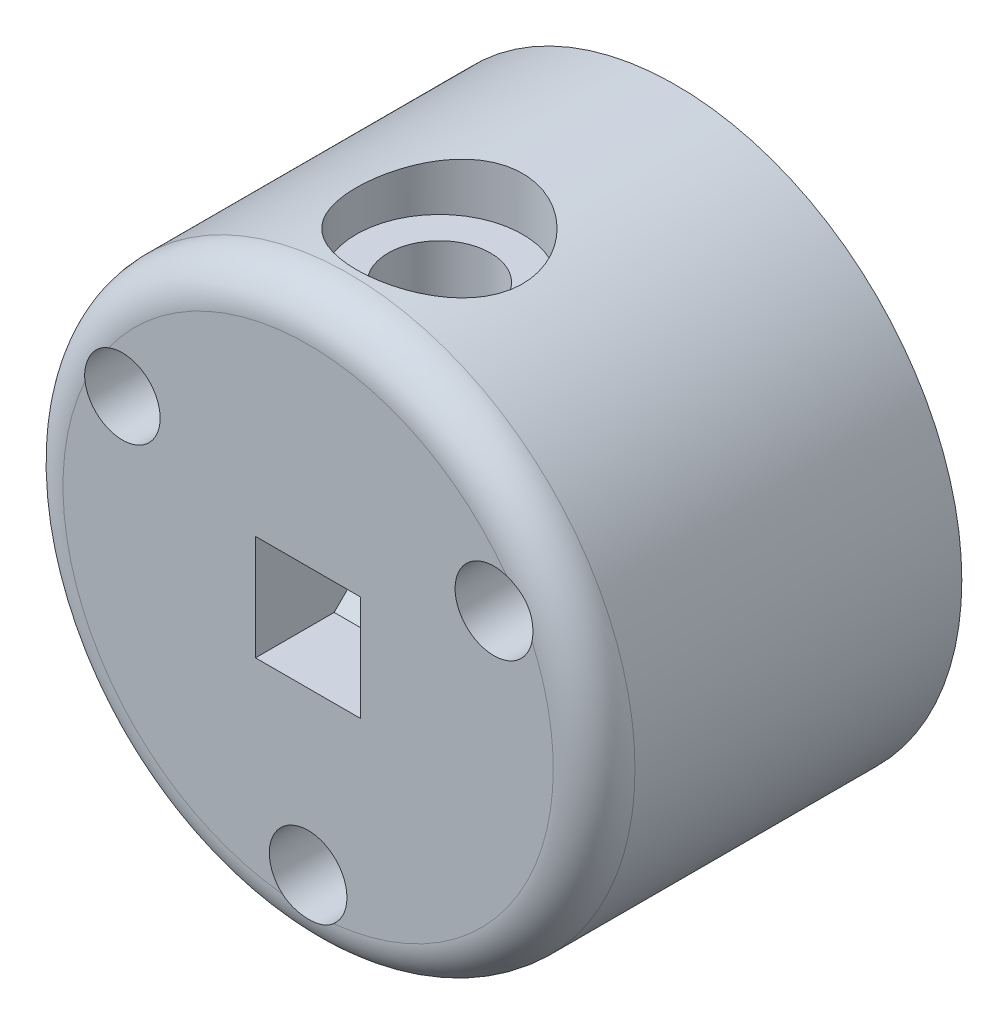
SolidWorks part; units mm, degrees
material "ABS"
ref_plane "前视基准面" through (0, 0, 0) normal (0, 0, 1) x (1, 0, 0)
ref_plane "上视基准面" through (0, 0, 0) normal (0, 1, 0) x (1, 0, 0)
ref_plane "右视基准面" through (0, 0, 0) normal (1, 0, 0) x (0, 0, -1)
sketch "草图1" plane through (0, 0, 0) normal (0, 0, 1) x (1, 0, 0)
  circle A0 centre (0, 0) radius 14
  dimension "D1" = 28
extrude "凸台-拉伸1" add sketch "草图1" along normal blind 22
sketch "草图2" plane through (0, 0, 22) normal (0, 0, 1) x (1, 0, 0)
  line L1 (0, 10.5) -> (-9.0933, 5.25) construction
  line L2 (-9.0933, 5.25) -> (-9.0933, -5.25) construction
  line L3 (-9.0933, -5.25) -> (0, -10.5) construction
  line L4 (0, -10.5) -> (9.0933, -5.25) construction
  line L5 (9.0933, -5.25) -> (9.0933, 5.25) construction
  line L6 (9.0933, 5.25) -> (0, 10.5) construction
  circle A0 centre (0, 0) radius 10.5 construction
  circle A2 centre (-9.0933, 5.25) radius 1.1
  circle A4 centre (9.0933, 5.25) radius 1.1
  circle A6 centre (0, -10.5) radius 1.1
  dimension "D1" = 21
sketch "草图3" plane through (0, 0, 0) normal (0, 0, -1) x (-1, 0, 0)
  circle A0 centre (0, 0) radius 7.35
  dimension "D1" = 14.7
extrude "切除-拉伸1" cut sketch "草图3" against normal blind 6
extrude "切除-拉伸2" cut sketch "草图2" against normal blind 32
sketch "草图4" plane through (0, 0, 22) normal (0, 0, 1) x (1, 0, 0)
  circle A7 centre (9.0933, 5.25) radius 1.9
  circle A9 centre (0, -10.5) radius 1.9
  circle A11 centre (-9.0933, 5.25) radius 1.85
  dimension "D1" = 3.8
extrude "切除-拉伸3" cut sketch "草图4" against normal blind 19
sketch "草图5" plane through (0, 0, 22) normal (0, 0, 1) x (1, 0, 0)
  line L1 (-2.575, -2.575) -> (2.575, -2.575)
  line L2 (-2.575, -2.575) -> (-2.575, 2.575)
  line L3 (-2.575, 2.575) -> (2.575, 2.575)
  line L4 (2.575, -2.575) -> (2.575, 2.575)
  line L5 (-2.575, -2.575) -> (2.575, 2.575) construction
  line L6 (-2.575, 2.575) -> (2.575, -2.575) construction
  point P0 (0, 0)
  dimension "D1" = 5.15
  dimension "D2" = 5.15
extrude "切除-拉伸4" cut sketch "草图5" against normal blind 13
sketch "草图6" plane through (-2.575, 0, 0) normal (1, 0, 0) x (0, 0, -1)
  line L0 (-9, -2.575) -> (-14.15, -2.575)
  line L1 (-9, -2.575) -> (-22, -2.575) construction
  line L2 (-14.15, -2.575) -> (-9, 2.575)
  line L3 (-9, 2.575) -> (-9, -2.575)
  dimension "D1" = 45
extrude "凸台-拉伸2" add sketch "草图6" along normal up to next
sketch "草图10" plane through (0, 0, 22) normal (0, 0, 1) x (1, 0, 0)
  line L0 (4, 13.4164) -> (-4, 13.4164) construction
  line L1 (2.575, 2.575) -> (-2.575, 2.575) construction
  circle A0 centre (0, 0) radius 14 construction
  dimension "D1" = 0
  dimension "D2" = 8
ref_plane "基准面1" through (0, 13.4164, 0) normal (0, 1, 0) x (1, 0, 0)
sketch "草图12" plane through (0, 0, 22) normal (0, 0, 1) x (1, 0, 0)
  circle A0 centre (0, 0) radius 19.2084
extrude "切除-拉伸9" cut sketch "草图12" against normal blind 4
fillet "圆角1" radius 2 1 edges at (14, 0, 18)
sketch "草图13" plane through (0, 5.7875, 5.7875) normal (0, 0.7071, 0.7071) x (1, 0, 0)
  line L0 (2.575, -8.1848) -> (-2.575, -8.1848)
  line L1 (2.575, -4.5432) -> (2.575, -11.8264) construction
  line L2 (-2.575, -4.5432) -> (-2.575, -11.8264) construction
sketch "草图14" plane through (0, 2.575, 0) normal (0, -1, 0) x (-1, 0, 0)
  line L0 (-2.575, -11.575) -> (2.575, -11.575) construction
  circle A0 centre (0, -11.575) radius 2.5
  dimension "D1" = 5
  dimension "D2" = 0
extrude "切除-拉伸10" cut sketch "草图14" against normal blind 18
sketch "草图15" plane through (0, 13.4164, 0) normal (0, 1, 0) x (1, 0, 0)
  circle A0 centre (0, -11.575) radius 4.075
  dimension "D1" = 8.15
extrude "切除-拉伸11" cut sketch "草图15" against normal mid plane 4
